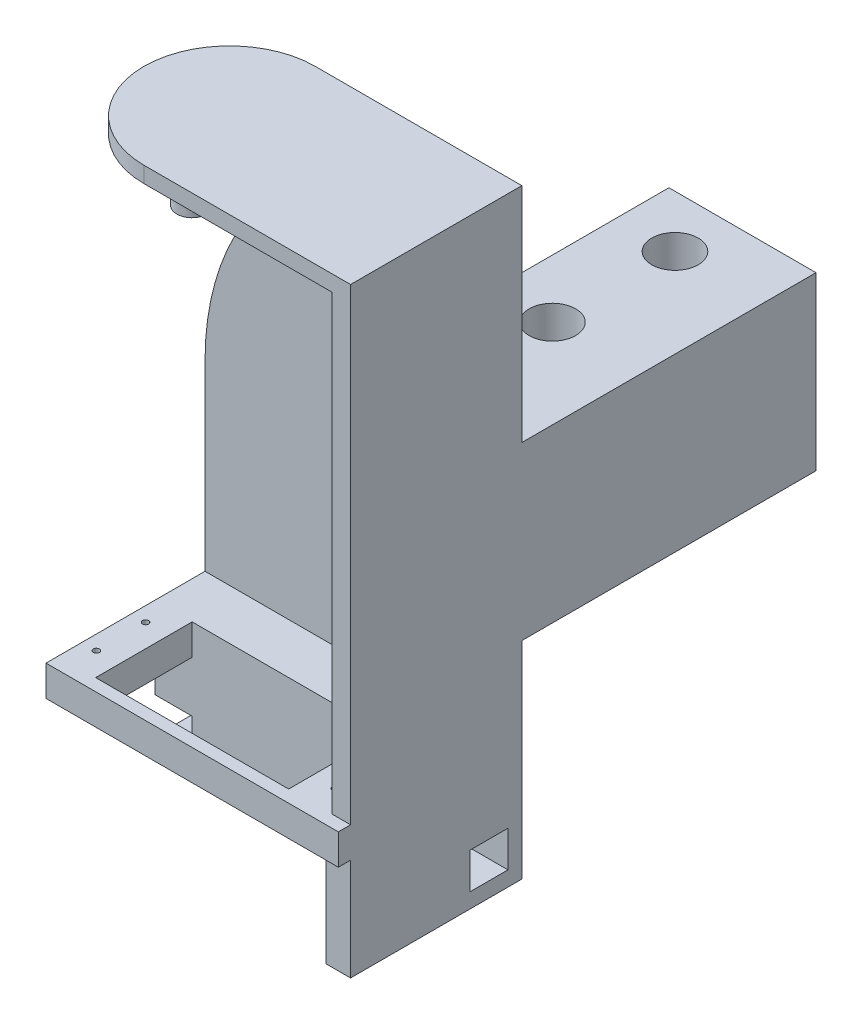
SolidWorks part; units mm, degrees
material "ABS"
ref_plane "Front Plane" through (0, 0, 0) normal (0, 0, 1) x (1, 0, 0)
ref_plane "Top Plane" through (0, 0, 0) normal (0, 1, 0) x (1, 0, 0)
ref_plane "Right Plane" through (0, 0, 0) normal (1, 0, 0) x (0, 0, -1)
sketch "Sketch1" plane through (0, 0, 0) normal (0, 1, 0) x (1, 0, 0)
  line L1 (0, 0) -> (55.494, 0)
  line L2 (0, 0) -> (0, 26.874)
  line L3 (0, 26.874) -> (55.494, 26.874)
  line L4 (55.494, 0) -> (55.494, 26.874)
  dimension "D1" = 55.494
  dimension "D2" = 26.874
extrude "Boss-Extrude1" add sketch "Sketch1" along normal blind 6.35
sketch "Sketch2" plane through (0, 6.35, 0) normal (0, 1, 0) x (1, 0, 0)
  line L0 (0, 0) -> (55.494, 0) construction
  line L1 (7.747, 0) -> (47.747, 0)
  line L2 (7.747, 0) -> (7.747, 19)
  line L3 (7.747, 19) -> (47.747, 19)
  line L4 (47.747, 0) -> (47.747, 19)
  line L5 (55.494, 26.874) -> (0, 26.874) construction
  point P8 (27.747, 26.874)
  point P9 (27.747, 19)
  dimension "D1" = 40
  dimension "D2" = 19
extrude "Cut-Extrude1" cut sketch "Sketch2" against normal blind 6.35
sketch "Sketch3" plane through (0, 0, 0) normal (0, -1, 0) x (1, 0, 0)
  circle A0 centre (2.997, -14.1) radius 0.635
  circle A1 centre (2.997, -3.9) radius 0.635
  circle A2 centre (52.497, -14.1) radius 0.635
  circle A3 centre (52.497, -3.9) radius 0.635
  dimension "D1" = 1.27
extrude "Cut-Extrude2" cut sketch "Sketch3" against normal blind 6.35
sketch "Sketch4" plane through (0, 0, 0) normal (0, -1, 0) x (1, 0, 0)
  line L0 (0, -26.874) -> (0, 0) construction
  line L1 (55.494, -26.874) -> (0, -26.874)
  line L2 (55.494, -26.874) -> (55.494, -19)
  line L3 (55.494, -19) -> (0, -19)
  line L4 (0, -26.874) -> (0, -19)
  line L5 (47.247, -19) -> (8.247, -19) construction
  dimension "D1" = 7.874
extrude "Boss-Extrude2" add sketch "Sketch4" along normal up to surface (21.15 mm away)
sketch "Sketch6" plane through (0, 0, 0) normal (0, 0, 1) x (1, 0, 0)
  line L1 (0, 0) -> (7.747, 0)
  line L2 (0, 0) -> (0, 6.35)
  line L3 (0, 6.35) -> (7.747, 6.35)
  line L4 (7.747, 0) -> (7.747, 6.35)
  line L5 (47.747, 0) -> (55.494, 0)
  line L6 (47.747, 0) -> (47.747, 6.35)
  line L7 (47.747, 6.35) -> (55.494, 6.35)
  line L8 (55.494, 0) -> (55.494, 6.35)
extrude "Boss-Extrude3" add sketch "Sketch6" along normal up to surface (1 mm away)
sketch "Sketch12" plane through (0, 0, -19) normal (0, 0, 1) x (1, 0, 0)
  line L0 (0, -21.15) -> (0, 0) construction
  line L1 (7.747, -18.05) -> (0, -18.05)
  line L2 (7.747, -18.05) -> (7.747, -10.575)
  line L3 (7.747, -10.575) -> (0, -10.575)
  line L4 (0, -18.05) -> (0, -10.575)
extrude "Cut-Extrude4" cut sketch "Sketch12" against normal blind 9.398
sketch "Sketch13" plane through (0, 0, -19) normal (0, 0, 1) x (1, 0, 0)
  line L1 (55.494, -21.15) -> (47.747, -21.15)
  line L2 (55.494, -21.15) -> (55.494, -13.25)
  line L3 (55.494, -13.25) -> (47.747, -13.25)
  line L4 (47.747, -21.15) -> (47.747, -13.25)
extrude "Boss-Extrude6" add sketch "Sketch13" along normal up to surface (20 mm away) up to face at (51.6205, 3.175, 1)
sketch "Sketch14" plane through (55.494, 0, 0) normal (1, 0, 0) x (0, 0, -1)
  line L1 (26.874, 6.35) -> (-1, 6.35)
  line L2 (26.874, 6.35) -> (26.874, -21.15)
  line L3 (26.874, -21.15) -> (-1, -21.15)
  line L4 (-1, 6.35) -> (-1, -21.15)
extrude "Boss-Extrude7" add sketch "Sketch14" along normal blind 5.08
sketch "Sketch16" plane through (0, 6.35, 0) normal (0, 1, 0) x (1, 0, 0)
  line L0 (60.574, -1) -> (47.747, -1) construction
  line L1 (60.574, 26.874) -> (56.764, 26.874)
  line L2 (60.574, 26.874) -> (60.574, -1)
  line L3 (60.574, -1) -> (56.764, -1)
  line L4 (56.764, 26.874) -> (56.764, -1)
  dimension "D1" = 3.81
extrude "Boss-Extrude8" add sketch "Sketch16" along normal up to surface (93.66 mm away)
sketch "Sketch17" plane through (0, 0, -26.874) normal (0, 0, -1) x (-1, 0, 0)
  line L0 (0, -21.15) -> (0, -18.05)
  line L1 (0, -18.05) -> (-7.747, -18.05)
  line L2 (-7.747, -18.05) -> (-7.747, -10.575)
  line L3 (-7.747, -10.575) -> (0, -10.575)
  line L4 (0, -10.575) -> (0, 6.35)
  line L5 (0, 6.35) -> (-56.764, 6.35)
  line L6 (-56.764, 6.35) -> (-56.764, 100.01)
  line L7 (-56.764, 100.01) -> (-60.574, 100.01)
  line L8 (-60.574, 100.01) -> (-60.574, -21.15)
  line L9 (-60.574, -21.15) -> (0, -21.15)
extrude "Boss-Extrude9" add sketch "Sketch17" along normal blind 7.62
sketch "Sketch18" plane through (56.764, 0, 0) normal (-1, 0, 0) x (0, 0, 1)
  line L0 (1, 100.01) -> (-34.494, 100.01) construction
  line L1 (-34.494, 6.35) -> (-29.414, 6.35)
  line L2 (-34.494, 6.35) -> (-34.494, 100.01)
  line L3 (-34.494, 100.01) -> (-29.414, 100.01)
  line L4 (-29.414, 6.35) -> (-29.414, 100.01)
  dimension "D1" = 5.08
extrude "Boss-Extrude10" add sketch "Sketch18" along normal up to surface (56.764 mm away) up to face at (0, -1.4083, -17.498)
sketch "Sketch19" plane through (0, 0, -34.494) normal (0, 0, -1) x (-1, 0, 0)
  line L0 (-60.574, 100.01) -> (-60.574, -21.15) construction
  line L1 (-60.574, 21.65) -> (-30.094, 21.65)
  line L2 (-60.574, 21.65) -> (-60.574, 57.21)
  line L3 (-60.574, 57.21) -> (-30.094, 57.21)
  line L4 (-30.094, 21.65) -> (-30.094, 57.21)
  point P6 (-60.574, 39.43)
  point P7 (-60.574, 39.43)
  dimension "D1" = 35.56
  dimension "D2" = 30.48
extrude "Boss-Extrude11" add sketch "Sketch19" along normal blind 76.2
sketch "Sketch20" plane through (0, 21.65, 0) normal (0, -1, 0) x (1, 0, 0)
  circle A0 centre (42.1502, -59.2531) radius 4.8133
  circle A1 centre (42.1502, -84.6531) radius 4.8133
  dimension "D1" = 9.6266
  dimension "D2" = 25.4
extrude "Cut-Extrude5" cut sketch "Sketch20" against normal blind 76.2
sketch "Sketch21" plane through (0, 0, -110.694) normal (0, 0, -1) x (-1, 0, 0)
  line L1 (-60.574, 21.65) -> (-30.094, 21.65)
  line L2 (-60.574, 21.65) -> (-60.574, 57.21)
  line L3 (-60.574, 57.21) -> (-30.094, 57.21)
  line L4 (-30.094, 21.65) -> (-30.094, 57.21)
extrude "Cut-Extrude6" cut sketch "Sketch21" against normal blind 15.24
sketch "Sketch23" plane through (7.747, 0, 0) normal (-1, 0, 0) x (0, 0, 1)
  line L0 (-34.494, -10.575) -> (-19, -10.575) construction
  line L1 (-31.6135, -10.575) -> (-23.7367, -10.575)
  line L2 (-31.6135, -10.575) -> (-31.6135, -18.05)
  line L3 (-31.6135, -18.05) -> (-23.7367, -18.05)
  line L4 (-23.7367, -10.575) -> (-23.7367, -18.05)
  line L5 (-34.494, -18.05) -> (-19, -18.05) construction
extrude "Cut-Extrude7" cut sketch "Sketch23" against normal blind 54.102
fillet "Fillet1" radius 55.88 1 edges at (0, 100.01, -31.954)
sketch "Sketch24" plane through (0, 100.01, 0) normal (0, 1, 0) x (1, 0, 0)
  line L1 (56.764, -1) -> (60.574, -1)
  line L2 (56.764, -1) -> (56.764, 34.494)
  line L3 (56.764, 34.494) -> (60.574, 34.494)
  line L4 (60.574, -1) -> (60.574, 34.494)
extrude "Boss-Extrude12" add sketch "Sketch24" along normal blind 3.302
sketch "Sketch25" plane through (56.764, 0, 0) normal (-1, 0, 0) x (0, 0, 1)
  line L1 (-34.494, 100.01) -> (1, 100.01)
  line L2 (-34.494, 100.01) -> (-34.494, 103.312)
  line L3 (-34.494, 103.312) -> (1, 103.312)
  line L4 (1, 100.01) -> (1, 103.312)
extrude "Boss-Extrude13" add sketch "Sketch25" along normal up to surface (56.764 mm away) up to face at (0, 9.9762, -20.477)
fillet "Fillet2" radius 17.78 2 edges at (0, 101.661, 1) (0, 101.661, -34.494)
sketch "Sketch26" plane through (0, 100.01, 0) normal (0, 1, 0) x (1, 0, 0)
  circle A0 centre (17.747, 9) radius 3.175
  dimension "D1" = 6.35
extrude "Boss-Extrude14" add sketch "Sketch26" against normal blind 8.89
sketch "Sketch27" plane through (0, -21.15, 0) normal (0, -1, 0) x (1, 0, 0)
  line L1 (47.747, 1) -> (55.494, 1)
  line L2 (47.747, 1) -> (47.747, -19)
  line L3 (47.747, -19) -> (55.494, -19)
  line L4 (55.494, 1) -> (55.494, -19)
  line L5 (47.747, -19) -> (0, -19) construction
extrude "Cut-Extrude9" cut sketch "Sketch27" against normal blind 10.668
sketch "Sketch28" plane through (0, 0, 1) normal (0, 0, 1) x (1, 0, 0)
  line L1 (55.494, 0) -> (47.747, 0)
  line L2 (55.494, 0) -> (55.494, 6.35)
  line L3 (55.494, 6.35) -> (47.747, 6.35)
  line L4 (47.747, 0) -> (47.747, 6.35)
extrude "Boss-Extrude15" add sketch "Sketch28" along normal blind 2.54
sketch "Sketch29" plane through (47.747, 0, 0) normal (-1, 0, 0) x (0, 0, 1)
  line L0 (3.54, 6.35) -> (-19, 6.35) construction
  line L1 (3.54, 0) -> (1, 0)
  line L2 (3.54, 0) -> (3.54, 6.35)
  line L3 (3.54, 6.35) -> (1, 6.35)
  line L4 (1, 0) -> (1, 6.35)
extrude "Boss-Extrude16" add sketch "Sketch29" along normal up to surface (47.747 mm away) up to face at (0, 9.9762, -20.477)
sketch "Sketch30" plane through (55.494, 0, 0) normal (1, 0, 0) x (0, 0, -1)
  line L1 (-3.54, 6.35) -> (-1, 6.35)
  line L2 (-3.54, 6.35) -> (-3.54, 0)
  line L3 (-3.54, 0) -> (-1, 0)
  line L4 (-1, 6.35) -> (-1, 0)
extrude "Boss-Extrude17" add sketch "Sketch30" along normal up to surface (5.08 mm away) up to face at (60.574, -14.3125, -27.6751)
